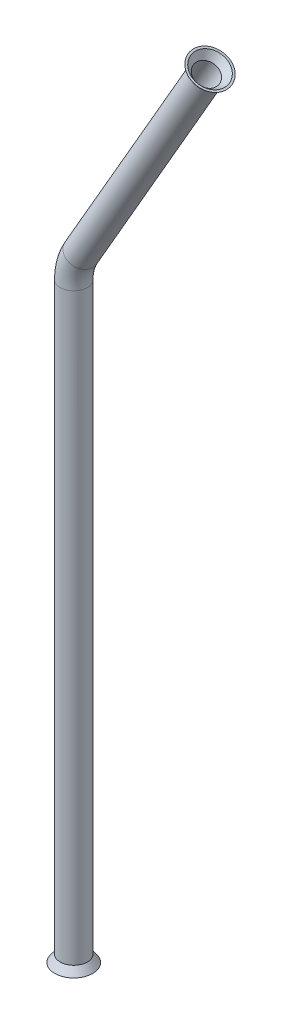
SolidWorks part; units mm, degrees
material "6061-T6 (SS)"
ref_plane "Front Plane" through (0, 0, 0) normal (0, 0, 1) x (1, 0, 0)
ref_plane "Top Plane" through (0, 0, 0) normal (0, 1, 0) x (1, 0, 0)
ref_plane "Right Plane" through (0, 0, 0) normal (1, 0, 0) x (0, 0, -1)
sketch "Sketch1" plane through (0, 0, 0) normal (0, 1, 0) x (1, 0, 0)
  circle A0 centre (0, 0) radius 4.826
  circle A1 centre (0, 0) radius 4.064
  dimension "D1" = 9.652
  dimension "D2" = 8.128
sketch "Sketch2" plane through (0, 0, 0) normal (0, 0, 1) x (1, 0, 0)
  line L0 (0, 0) -> (0, 206.9569)
  line L1 (2.5522, 216.4819) -> (47.0022, 293.4716)
  arc A0 (0, 206.9569) -> (2.5522, 216.4819) centre (19.05, 206.9569) cw
  dimension "D1" = 44.45
  dimension "D2" = 150
  dimension "D4" = 293.4716
  dimension "D3" = 19.05
sweep "Sweep1" add profiles "Sketch1" path "Sketch2"
sketch "Sketch3" plane through (0, 0, 0) normal (0, -1, 0) x (1, 0, 0)
  circle A0 centre (0, 0) radius 4.826
  circle A1 centre (0, 0) radius 4.826 construction
extrude "Boss-Extrude1" add sketch "Sketch3" along normal blind 2.54 draft 37 draft outward yes
sketch "Sketch4" plane through (0, -2.54, 0) normal (0, -1, 0) x (1, 0, 0)
  line L0 (-4.826, 0) -> (-4.064, 0) construction
  line L1 (-5.978, 0) -> (-6.74, 0) construction
  circle A0 centre (0, 0) radius 5.978
  circle A1 centre (0, 0) radius 4.826 construction
  circle A2 centre (0, 0) radius 4.064 construction
  circle A3 centre (0, 0) radius 6.74 construction
extrude "Cut-Extrude1" cut sketch "Sketch4" against normal through all draft 37
sketch "Sketch5" plane through (138.8275, 240.4563, 0) normal (0.5, 0.866, 0) x (0, 0, -1)
  circle A1 centre (0, 106.0307) radius 4.826
  circle A2 centre (0, 106.0307) radius 4.826 construction
  circle A3 centre (0, 106.0307) radius 4.826 construction
extrude "Boss-Extrude2" add sketch "Sketch5" along normal blind 2.54 draft 37 draft outward yes
sketch "Sketch6" plane through (140.0975, 242.656, 0) normal (0.5, 0.866, 0) x (0, 0, -1)
  line L0 (-5.978, 106.0307) -> (-6.74, 106.0307) construction
  circle A0 centre (0, 106.0307) radius 5.978
  circle A1 centre (0, 106.0307) radius 6.74 construction
  dimension "D1" = 0.762
extrude "Cut-Extrude2" cut sketch "Sketch6" against normal through all draft 37
